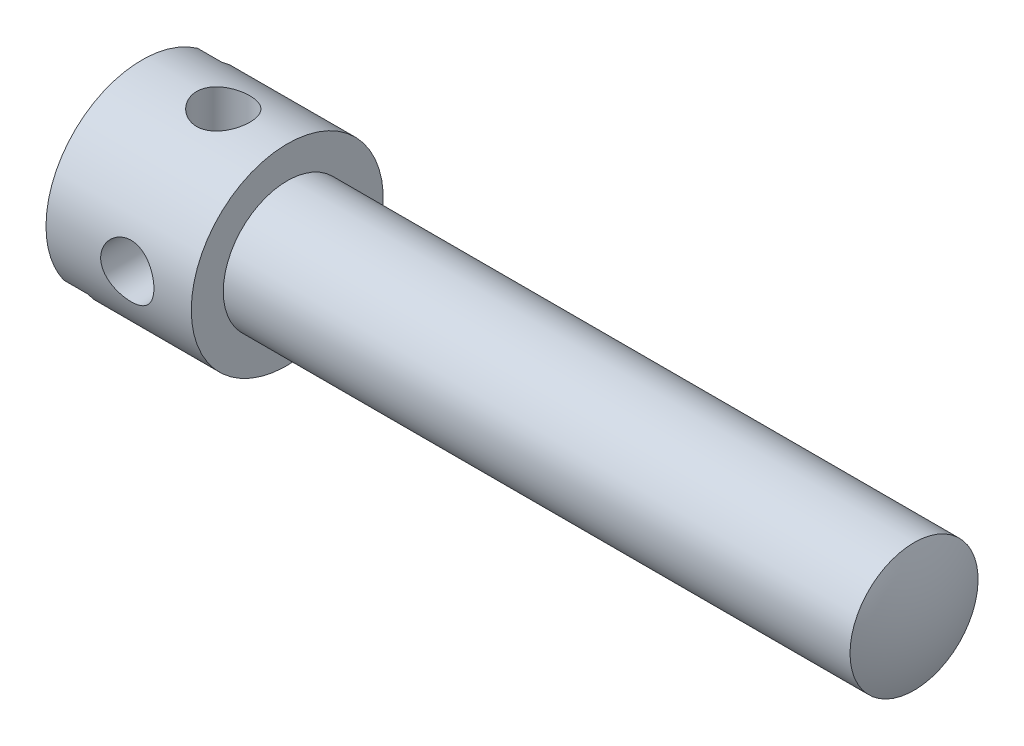
SolidWorks part; units mm, degrees
ref_plane "Front" through (0, 0, 0) normal (0, 0, 1) x (1, 0, 0)
ref_plane "Top" through (0, 0, 0) normal (0, 1, 0) x (1, 0, 0)
ref_plane "Right" through (0, 0, 0) normal (1, 0, 0) x (0, 0, -1)
sketch "Sketch1" plane through (0, 0, 0) normal (0, 0, 1) x (1, 0, 0)
  line L0 (-25.0595, 0) -> (22.8592, 0) construction
  line L1 (1.1515, 7.5) -> (12.5, 7.5)
  line L2 (0, 0) -> (12.5, 0)
  line L4 (12.5, 7.5) -> (12.5, 0)
  arc A0 (1.1515, 7.5) -> (0, 0) centre (25, 0) ccw
revolve "BaseHead" add sketch "Sketch1" angle 360 about L0
sketch "Sketch2" plane through (12.5, 3.6143, 0.1956) normal (1, 0, 0) x (0, 0, -1)
  circle A0 centre (0.1956, -3.6143) radius 5
extrude "Neck" add sketch "Sketch2" along normal blind 50
cosmetic thread "ThreadCosmetic1" [suppressed] parameters "D1"=30, "D2"=8.5
sketch "Sketch3" plane through (62.5, 0.8938, 2.2293) normal (1, 0, 0) x (0, 0, -1)
  circle A0 centre (2.2293, -0.8938) radius 5
  dimension "d" = 10
sketch "Sketch4" plane through (0, 0, 0) normal (0, 0, 1) x (1, 0, 0)
  line L0 (61.4142, 0) -> (-35.076, 0) construction
  line L1 (62.5, -5) -> (62.5, 5) construction
  line L3 (62.5, 0) -> (62.5, 5) construction
  line L4 (50, 12.5) -> (50, 17.5)
  line L5 (50, 17.5) -> (67.5, 17.5)
  line L6 (67.5, 17.5) -> (67.5, 0)
  line L7 (67.5, 0) -> (62.5, 0)
  arc A0 (62.5, 0) -> (50, 12.5) centre (50, 0) ccw
  dimension "D3" = 12.5
  dimension "D1" = 5
  dimension "D2" = 5
revolve "Cut-Revolve1" cut sketch "Sketch4" angle 360 about L0
sketch "Sketch5" plane through (0, 0, 0) normal (0, 0, 1) x (1, 0, 0)
  line L0 (12.5, -7.5) -> (12.5, 7.5) construction
  circle A0 centre (7.5, 0) radius 2.08
extrude "Cut-Extrude1" cut sketch "Sketch5" against normal mid plane 140
sketch "Sketch6" plane through (0, 0, 0) normal (0, 1, 0) x (1, 0, 0)
  line L0 (12.5, -7.5) -> (12.5, 7.5) construction
  circle A0 centre (7.5, 0) radius 2.08
extrude "Cut-Extrude2" cut sketch "Sketch6" against normal mid plane 140
ref_plane "Plane1" through (0, 0, 0) normal (0, -0.7071, 0.7071) x (1, 0, 0)
sketch "Sketch7" plane through (0, 0, 0) normal (0, -0.7071, 0.7071) x (1, 0, 0)
  line L0 (0, 0) -> (-23.3893, 0) construction
  line L1 (0, 1.25) -> (3, 1.25)
  line L2 (0, 1.25) -> (0, -1.25)
  line L3 (0, -1.25) -> (3, -1.25)
  line L4 (3, 1.25) -> (3, -1.25)
  line L6 (1.1515, 7.5) -> (1.1515, -7.5) construction
  arc A1 (0, 0) -> (1.1515, -7.5) centre (25, 0) ccw construction
extrude "Cut-Extrude3" cut sketch "Sketch7" against normal mid plane 140
sketch "Sketch8" plane through (0, 0, 0) normal (0, 1, 0) x (1, 0, 0)
  line L0 (0, 0) -> (-28.8801, 0) construction
  line L2 (0, 1.25) -> (3, 1.25)
  line L3 (0, 1.25) -> (0, -1.25)
  line L4 (0, -1.25) -> (3, -1.25)
  line L5 (3, 1.25) -> (3, -1.25)
extrude "Cut-Extrude4" [suppressed] cut sketch "Sketch8" against normal mid plane 140
sketch "Sketch9" plane through (0, 0, 0) normal (0, 0, 1) x (1, 0, 0)
  line L0 (61.4564, 4.3505) -> (61.8314, 5)
  line L1 (61.8314, 5) -> (61.8314, 5.75)
  line L2 (61.8314, 5.75) -> (61.0814, 5.75)
  line L3 (61.0814, 5.75) -> (61.0814, 5)
  line L4 (61.0814, 5) -> (61.4564, 4.3505)
  line L5 (0, 0) -> (68.448, 0) construction
  line L7 (61.4564, 5) -> (61.4564, -5) construction
  dimension "D1" = 10
  dimension "D2" = 0.75
revolve "Cut-Revolve10" [suppressed] cut sketch "Sketch9" angle 360 about L5
pattern_linear "LPattern10" [suppressed] count 33 spacing 0.9 along (-1, 0, 0) of bodies 109
equation "\"D3@Sketch4\" = \"R@Sketch1\"  / 2"
equation "\"D1@Sketch9\" = \"d@Sketch2\""
equation "\"D2@Sketch9\" =  ( \"d@Sketch2\" - \"D2@ThreadCosmetic1\" )  / 2"
equation "\"D3@LPattern10\" = \"D2@Sketch9\" * 1.2"
equation "\"D1@LPattern10\" = \"D1@ThreadCosmetic1\" / \"D3@LPattern10\""
